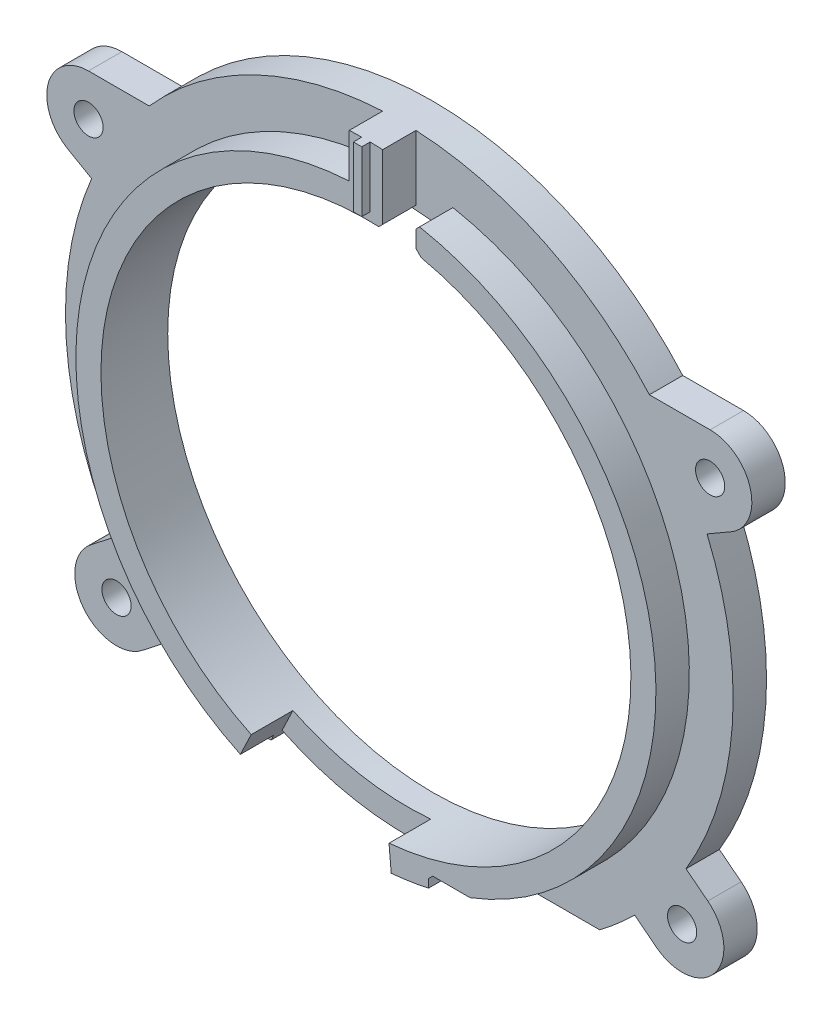
SolidWorks part; units mm, degrees
ref_plane "前视基准面" through (0, 0, 0) normal (0, 0, 1) x (1, 0, 0)
ref_plane "上视基准面" through (0, 0, 0) normal (0, 1, 0) x (1, 0, 0)
ref_plane "右视基准面" through (0, 0, 0) normal (1, 0, 0) x (0, 0, -1)
sketch "草图1" plane through (0, 0, 0) normal (0, 0, 1) x (1, 0, 0)
  circle A0 centre (0, 0) radius 31.75
  circle A1 centre (0, 0) radius 40
  dimension "D1" = 63.5
  dimension "D2" = 80
extrude "凸台-拉伸1" add sketch "草图1" along normal blind 4
sketch "草图2" plane through (0, 0, 4) normal (0, 0, 1) x (1, 0, 0)
  line L0 (0, 0) -> (0, -40) construction
  line L1 (0, 0) -> (-33.8845, -26.4734) construction
  line L2 (-36.9628, -22.5334) -> (-34.3515, -20.4933)
  line L3 (-30.8062, -30.4135) -> (-28.1949, -28.3734)
  line L4 (0, 0) -> (33.8845, -26.4734) construction
  line L5 (30.8062, -30.4135) -> (28.1949, -28.3734)
  line L6 (36.9628, -22.5334) -> (34.3515, -20.4933)
  circle A0 centre (0, 0) radius 40 construction
  circle A1 centre (-33.8845, -26.4734) radius 1.75
  arc A2 (-36.9628, -22.5334) -> (-30.8062, -30.4135) centre (-33.8845, -26.4734) ccw
  arc A3 (-34.3515, -20.4933) -> (-28.1949, -28.3734) centre (0, 0) ccw
  arc A4 (34.3515, -20.4933) -> (28.1949, -28.3734) centre (0, 0) cw
  arc A5 (36.9628, -22.5334) -> (30.8062, -30.4135) centre (33.8845, -26.4734) cw
  circle A6 centre (33.8845, -26.4734) radius 1.75
  dimension "D1" = 3.5
  dimension "D2" = 10
  dimension "D3" = 43
  dimension "D4" = 52
extrude "凸台-拉伸2" add sketch "草图2" against normal up to surface (4 mm away) up to face at (40, 0, 0)
sketch "草图3" plane through (0, 0, 4) normal (0, 0, 1) x (1, 0, 0)
  line L1 (-24, -32) -> (-15.3704, -32)
  line L2 (15.3704, -32) -> (24, -32)
  circle A2 centre (0, 0) radius 40 construction
  arc A3 (-24, -32) -> (24, -32) centre (0, 0) ccw
  circle A4 centre (0, 0) radius 35.5 construction
  arc A5 (15.3704, -32) -> (-15.3704, -32) centre (0, 0) cw
  dimension "D2" = 71
  dimension "D1" = 32
extrude "切除-拉伸2" cut sketch "草图3" against normal through all
sketch "草图4" plane through (0, 0, 4) normal (0, 0, 1) x (1, 0, 0)
  line L0 (0, 0) -> (0, 40) construction
  line L1 (-37.2391, 21.5) -> (0, 0) construction
  line L2 (-37.2391, 26.5) -> (-29.9625, 26.5)
  line L3 (-39.7391, 17.1699) -> (-36.8693, 15.513)
  line L4 (37.2391, 21.5) -> (0, 0) construction
  line L5 (39.7391, 17.1699) -> (36.8693, 15.513)
  line L6 (37.2391, 26.5) -> (29.9625, 26.5)
  circle A0 centre (0, 0) radius 40 construction
  circle A1 centre (-37.2391, 21.5) radius 1.75
  arc A2 (-37.2391, 26.5) -> (-39.7391, 17.1699) centre (-37.2391, 21.5) ccw
  arc A3 (-29.9625, 26.5) -> (-36.8693, 15.513) centre (0, 0) ccw
  arc A4 (29.9625, 26.5) -> (36.8693, 15.513) centre (0, 0) cw
  arc A5 (37.2391, 26.5) -> (39.7391, 17.1699) centre (37.2391, 21.5) cw
  circle A6 centre (37.2391, 21.5) radius 1.75
  dimension "D1" = 3.5
  dimension "D2" = 10
  dimension "D3" = 43
  dimension "D4" = 60
extrude "凸台-拉伸3" add sketch "草图4" against normal up to surface (4 mm away) up to face at (0, -23.4113, 0)
sketch "草图5" plane through (0, 0, 4) normal (0, 0, -1) x (-1, 0, 0)
  circle A0 centre (0, 0) radius 31.75
  circle A1 centre (0, 0) radius 34.75
  circle A2 centre (0, 0) radius 31.75 construction
  dimension "D1" = 3
extrude "凸台-拉伸4" add sketch "草图5" against normal blind 4
sketch "草图6" plane through (0, 0, 4) normal (0, 0, 1) x (1, 0, 0)
  line L0 (-15.0457, -31.3239) -> (-13.7468, -28.6197)
  line L2 (2.7672, -31.6292) -> (3.0287, -34.6178)
  line L3 (0, 0) -> (0, -35.5) construction
  circle A0 centre (0, 0) radius 31.75 construction
  arc A1 (-13.7468, -28.6197) -> (2.7672, -31.6292) centre (0, 0) ccw
  circle A2 centre (0, 0) radius 34.75 construction
  arc A3 (-15.0457, -31.3239) -> (3.0287, -34.6178) centre (0, 0) ccw
  arc A4 (-15.3704, -32) -> (15.3704, -32) centre (0, 0) ccw construction
  dimension "D1" = 5
extrude "切除-拉伸3" cut sketch "草图6" along normal through all
sketch "草图7" plane through (0, 0, 4) normal (0, 0, 1) x (1, 0, 0)
  line L0 (-2, 39.95) -> (-2, 34.6924)
  line L1 (0, 40) -> (0, 0) construction
  line L2 (2, 39.95) -> (2, 34.6924)
  arc A0 (29.9625, 26.5) -> (-29.9625, 26.5) centre (0, 0) ccw construction
  arc A1 (3.0287, -34.6178) -> (-15.0457, -31.3239) centre (0, 0) ccw construction
  arc A2 (2, 34.6924) -> (-2, 34.6924) centre (0, 0) ccw
  arc A3 (2, 39.95) -> (-2, 39.95) centre (0, 0) ccw
  dimension "D1" = 2
extrude "凸台-拉伸5" add sketch "草图7" along normal up to surface (4 mm away) up to face at (0.106, 0.5818, 8)
sketch "草图8" plane through (0, 0, 8) normal (0, 0, 1) x (1, 0, 0)
  line L0 (-0.5, 39.9969) -> (-0.5, 31.7461)
  line L1 (0, 0) -> (0, 40) construction
  line L2 (0.5, 39.9969) -> (0.5, 31.7461)
  arc A0 (2, 39.95) -> (-2, 39.95) centre (0, 0) ccw construction
  arc A1 (2.7672, -31.6292) -> (-13.7468, -28.6197) centre (0, 0) ccw construction
  arc A2 (0.5, 31.7461) -> (-0.5, 31.7461) centre (0, 0) ccw
  arc A3 (0.5, 39.9969) -> (-0.5, 39.9969) centre (0, 0) ccw
  dimension "D1" = 0.5
extrude "凸台-拉伸6" add sketch "草图8" along normal blind 1
sketch "草图9" plane through (0, 0, 4) normal (0, 0, 1) x (1, 0, 0)
  line L0 (-15.0457, -31.3239) -> (-15.3704, -32)
  line L1 (3.0287, -34.6178) -> (3.094, -35.3649)
  line L2 (3.0287, -34.6178) -> (2.7672, -31.6292) construction
  line L3 (-13.7468, -28.6197) -> (-15.0457, -31.3239) construction
  arc A0 (-15.3704, -32) -> (15.3704, -32) centre (0, 0) ccw construction
  arc A3 (-15.3704, -32) -> (3.094, -35.3649) centre (0, 0) ccw
  arc A4 (-15.0457, -31.3239) -> (3.0287, -34.6178) centre (0, 0) ccw
extrude "切除-拉伸4" cut sketch "草图9" against normal blind 2
sketch "草图10" plane through (0, 0, 4) normal (0, 0, 1) x (1, 0, 0)
  line L4 (3.0287, -34.6178) -> (2.7672, -31.6292)
  line L5 (-13.7468, -28.6197) -> (-15.0457, -31.3239)
  line L6 (3.0287, -34.6178) -> (2.7672, -31.6292)
  line L7 (-13.7468, -28.6197) -> (-15.0457, -31.3239)
  arc A4 (-15.0457, -31.3239) -> (3.0287, -34.6178) centre (0, 0) ccw
  arc A5 (-13.7468, -28.6197) -> (2.7672, -31.6292) centre (0, 0) ccw
  arc A6 (-15.0457, -31.3239) -> (3.0287, -34.6178) centre (0, 0) ccw
  arc A7 (-13.7468, -28.6197) -> (2.7672, -31.6292) centre (0, 0) ccw
  dimension "D1" = 0
extrude "切除-拉伸5" cut sketch "草图10" against normal blind 1
chamfer "倒角1" distance 1 angle 45 1 edges at (-6.2301, -34.187, 2)
sketch "草图11" plane through (0, 0, 8) normal (0, 0, 1) x (1, 0, 0)
  line L1 (7.5, -33.931) -> (12.4817, -33.931)
  line L2 (7.5, -33.931) -> (7.5, -32.431)
  line L3 (7.5, -32.431) -> (12.4817, -32.431)
  line L4 (12.4817, -33.931) -> (12.4817, -32.431)
  arc A0 (3.0287, -34.6178) -> (2, 34.6924) centre (0, 0) ccw construction
  arc A1 (3.0287, -34.6178) -> (2, 34.6924) centre (0, 0) ccw construction
  dimension "D1" = 7.5
  dimension "D2" = 1.5
extrude "切除-拉伸6" cut sketch "草图11" against normal up to surface (4 mm away) up to face at (-28.5647, -2.4177, 4)
chamfer "倒角2" distance 0.5 angle 45 1 edges at (7.5, -32.431, 6)
sketch "草图12" plane through (0, 0, 4) normal (0, 0, 1) x (1, 0, 0)
  line L1 (2, 34.6924) -> (6, 34.6924)
  line L2 (2, 34.6924) -> (2, 31.1779)
  line L3 (2, 31.1779) -> (6, 31.1779)
  line L4 (6, 34.6924) -> (6, 31.1779)
  arc A0 (2.7672, -31.6292) -> (0.5, 31.7461) centre (0, 0) ccw construction
  dimension "D1" = 4
extrude "切除-拉伸7" cut sketch "草图12" along normal up to surface (4 mm away) up to face at (-13.8749, 16.1239, 8)
chamfer "倒角3" distance 0.5 angle 45 3 edges at (6, 31.1779, 6) (2, 31.6869, 6) (6, 34.2281, 6) first distance on face at (6, 32.703, 6) first distance on face at (2, 35.8185, 6)
sketch "草图13" plane through (0, 0, 8) normal (0, 0, 1) x (1, 0, 0)
  line L0 (0.5, 31.7461) -> (0.5, 39.9969) construction
  line L1 (-0.5, 31.7461) -> (0.5, 31.7461)
  line L2 (-0.5, 31.7461) -> (-0.5, 32.7461)
  line L3 (-0.5, 32.7461) -> (0.5, 32.7461)
  line L4 (0.5, 31.7461) -> (0.5, 32.7461)
  dimension "D1" = 1
extrude "切除-拉伸8" cut sketch "草图13" along normal up to surface (1 mm away) up to face at (0, 35.8732, 9)
